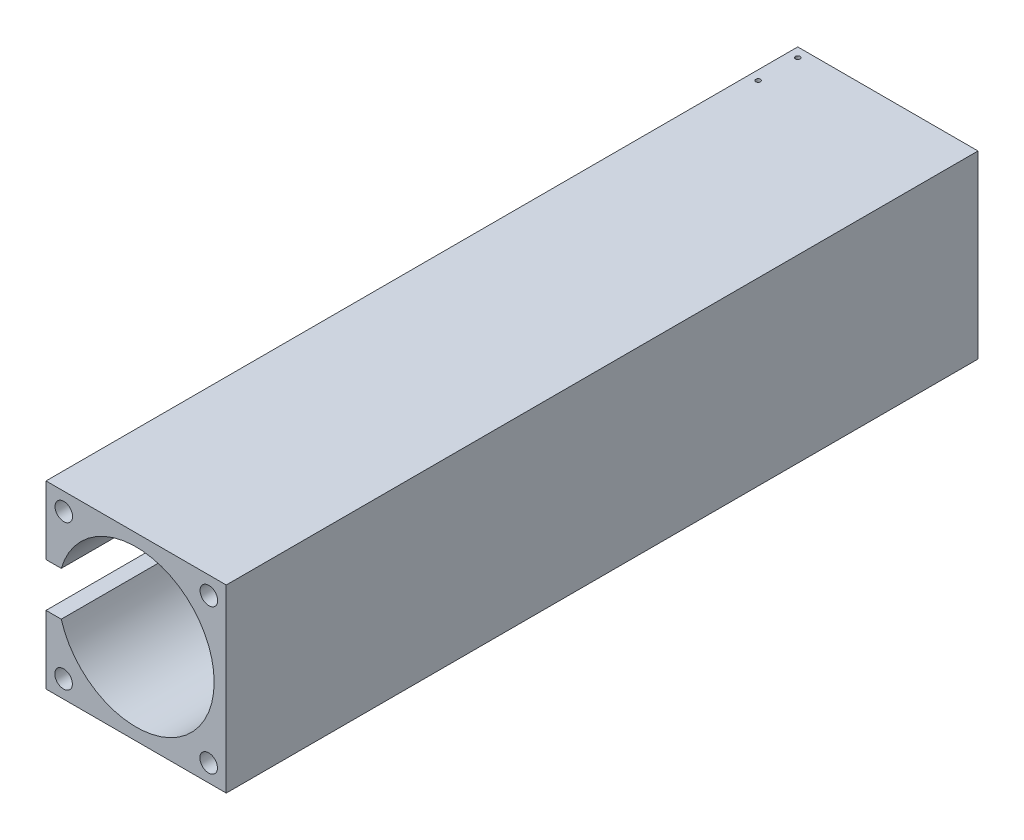
SolidWorks part; units mm, degrees
ref_plane "前基準面" through (0, 0, 0) normal (0, 0, 1) x (1, 0, 0)
ref_plane "上基準面" through (0, 0, 0) normal (0, 1, 0) x (1, 0, 0)
ref_plane "右基準面" through (0, 0, 0) normal (1, 0, 0) x (0, 0, -1)
ref_axis "基準軸1" through (0, -55, 0) along (0, 1, 0)
ref_axis "基準軸2" through (-88.99, 0, 0) along (1, 0, 0)
ref_axis "基準軸3" through (0, 0, 55) along (0, 0, -1)
sketch "草圖1" plane through (0, 0, 0) normal (0, 0, 1) x (1, 0, 0)
  line L0 (0, -55) -> (0, 55) construction
  line L1 (-41, -41) -> (41, -41)
  line L2 (-41, -41) -> (-41, 41)
  line L3 (-41, 41) -> (41, 41)
  line L4 (41, -41) -> (41, 41)
  line L5 (55, 0) -> (-55, 0) construction
  circle A0 centre (0, 0) radius 35.5
  point P7 (0, -41)
  point P10 (41, 0)
  dimension "D1" = 71
  dimension "D2" = 82
  dimension "D3" = 82
extrude "填料-伸長1" add sketch "草圖1" along normal blind 315
sketch "草圖2" plane through (0, 0, 0) normal (0, 0, -1) x (-1, 0, 0)
  line L1 (-41, 41) -> (41, 41)
  line L2 (-41, 41) -> (-41, -41)
  line L3 (-41, -41) -> (41, -41)
  line L4 (41, 41) -> (41, -41)
extrude "填料-伸長2" add sketch "草圖2" along normal blind 27
ref_plane "平面1" through (0, 0, -13.5) normal (0, 0, -1) x (-1, 0, 0)
sketch "草圖3" plane through (0, 0, 315) normal (0, 0, 1) x (1, 0, 0)
  line L0 (-41, 41) -> (-41, -41) construction
  line L1 (-41, 10) -> (-33, 10)
  line L2 (-41, 10) -> (-41, -10)
  line L3 (-41, -10) -> (-33, -10)
  line L4 (-33, 10) -> (-33, -10)
  line L6 (45.1, 0) -> (-45.1, 0) construction
  point P6 (-33, 0)
  dimension "D1" = 8
  dimension "D2" = 20
extrude "除料-伸長1" cut sketch "草圖3" against normal up to surface (315 mm away) up to face at (35.5, 0, 0)
sketch "草圖4" plane through (0, 0, 315) normal (0, 0, 1) x (1, 0, 0)
  line L1 (41, 41) -> (-41, 41) construction
  line L2 (-41, 41) -> (-41, 10) construction
  line L3 (-41, -41) -> (41, -41) construction
  line L4 (-41, -10) -> (-41, -41) construction
  circle A0 centre (-32.9, 33) radius 4
  circle A1 centre (33.1, 32.9) radius 4
  circle A2 centre (33, -33.1) radius 4
  circle A3 centre (-33, -33) radius 4
  point P15 (0.05, -0.05)
  dimension "D1" = 8
  dimension "D5" = 8
  dimension "D2" = 8
  dimension "D3" = 8.1
  dimension "D6" = 8
  dimension "D4" = 4
extrude "除料-伸長2" cut sketch "草圖4" against normal blind 20
fillet "圓角2" radius 3 1 edges at (-28.9, 33, 295)
fillet "圓角3" radius 3 1 edges at (37.1, 32.9, 295)
fillet "圓角4" radius 3 1 edges at (-29, -33, 295)
fillet "圓角5" radius 3 1 edges at (37, -33.1, 295)
sketch "草圖5" plane through (0, 41, 0) normal (0, 1, 0) x (1, 0, 0)
  line L0 (-41, -315) -> (-41, 27) construction
  line L4 (-41, 27) -> (41, 27) construction
  circle A2 centre (-36.75, 22.75) radius 1.05
  circle A3 centre (-36.75, 4.75) radius 1.05
  dimension "D1" = 18
  dimension "D2" = 2.1
  dimension "D3" = 2.1
  dimension "D4" = 4.25
  dimension "D5" = 4.25
  dimension "D6" = 4.25
extrude "除料-伸長3" cut sketch "草圖5" against normal blind 10
ref_plane "平面2" through (0, 35, 0) normal (0, 1, 0) x (1, 0, 0)
sketch "草圖6" plane through (0, 35, 0) normal (0, 1, 0) x (1, 0, 0)
  circle A0 centre (-36.75, 22.75) radius 1.05
  circle A1 centre (-36.75, 4.75) radius 1.05
  dimension "D1" = 2.1
  dimension "D2" = 2.1
extrude "填料-伸長3" add sketch "草圖6" along normal blind 0.2
